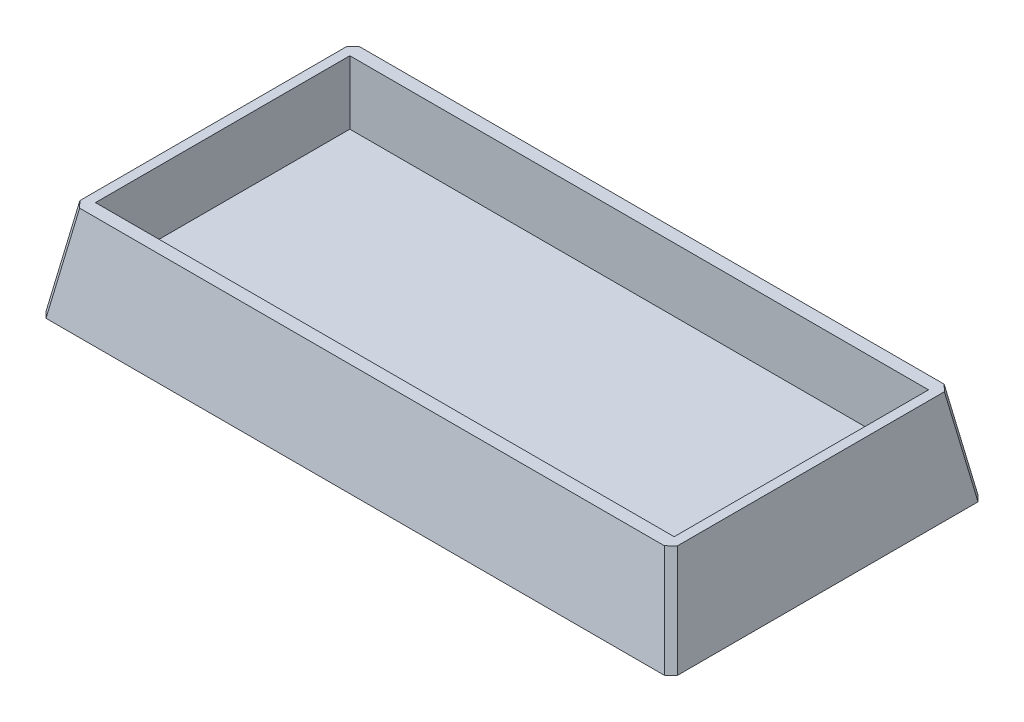
SolidWorks part; units mm, degrees
ref_plane "Front Plane" through (0, 0, 0) normal (0, 0, 1) x (1, 0, 0)
ref_plane "Top Plane" through (0, 0, 0) normal (0, 1, 0) x (1, 0, 0)
ref_plane "Right Plane" through (0, 0, 0) normal (1, 0, 0) x (0, 0, -1)
sketch "Sketch2" plane through (0, 0, 0) normal (0, 1, 0) x (1, 0, 0)
  line L1 (-50, 25) -> (50, 25)
  line L2 (-50, 25) -> (-50, -25)
  line L3 (-50, -25) -> (50, -25)
  line L4 (50, 25) -> (50, -25)
  line L5 (-50, 25) -> (50, -25) construction
  line L6 (-50, -25) -> (50, 25) construction
  line L7 (-45.5, 20) -> (45.5, 20)
  line L8 (-45.5, 20) -> (-45.5, -20)
  line L9 (-45.5, -20) -> (45.5, -20)
  line L10 (45.5, 20) -> (45.5, -20)
  line L11 (-45.5, 20) -> (45.5, -20) construction
  line L12 (-45.5, -20) -> (45.5, 20) construction
  point P0 (0, 0)
  point P5 (0, 0)
extrude "Boss-Extrude1" add sketch "Sketch2" along normal blind 10
sketch "Sketch3" plane through (0, 0, 0) normal (0, -1, 0) x (1, 0, 0)
  line L1 (-50, -25) -> (50, -25)
  line L2 (-50, -25) -> (-50, 25)
  line L3 (-50, 25) -> (50, 25)
  line L4 (50, -25) -> (50, 25)
  line L5 (-50, -25) -> (50, 25) construction
  line L6 (-50, 25) -> (50, -25) construction
  point P0 (0, 0)
extrude "Boss-Extrude2" add sketch "Sketch3" along normal blind 5
chamfer "Chamfer1" distance 17 angle 10 4 edges at (-50, 10, 0) (0, 10, -25) (50, 10, 0) (0, 10, 25) first distance on face at (-50, 2.5, 0) first distance on face at (0, 2.5, -25) first distance on face at (50, 2.5, 0) first distance on face at (0, 2.5, 25)
chamfer "Chamfer2" distance 1 angle 45 4 edges at (-48.3249, 2.5, -23.3249) (48.3249, 2.5, -23.3249) (48.3249, 2.5, 23.3249) (-48.3249, 2.5, 23.3249) first distance on face at (0, 2.5, -23.3249) first distance on face at (48.3249, 2.5, 0) first distance on face at (0, 2.5, 23.3249)
